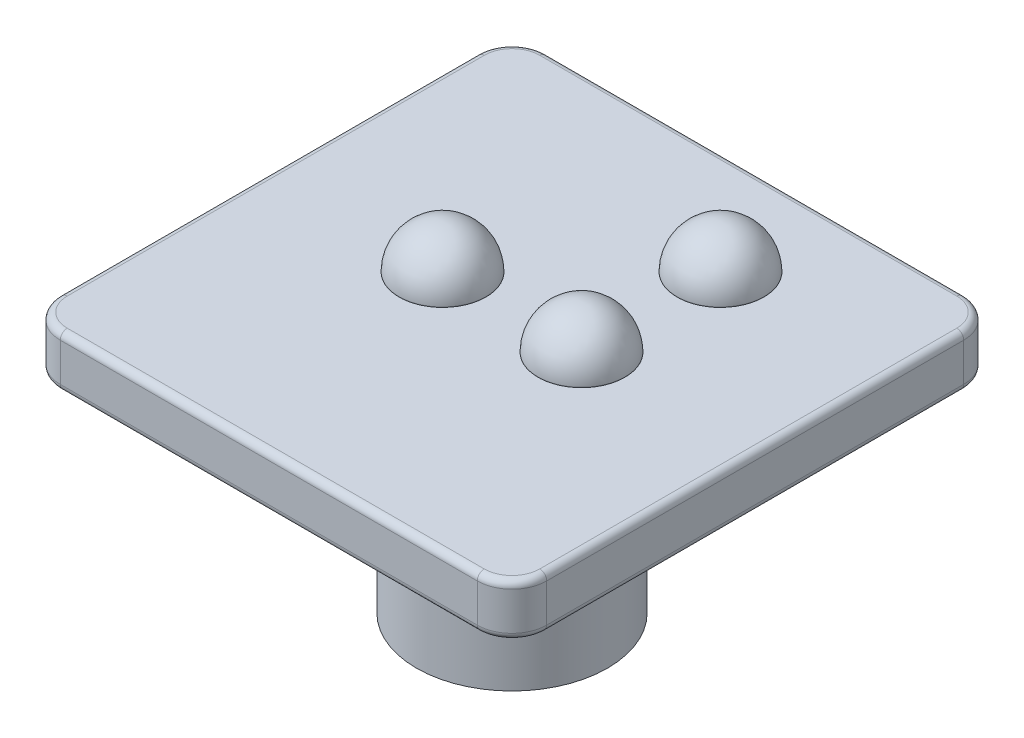
SolidWorks part; units mm, degrees
ref_plane "Front Plane" through (0, 0, 0) normal (0, 0, 1) x (1, 0, 0)
ref_plane "Top Plane" through (0, 0, 0) normal (0, 1, 0) x (1, 0, 0)
ref_plane "Right Plane" through (0, 0, 0) normal (1, 0, 0) x (0, 0, -1)
sketch "Sketch1" plane through (0, 0, 0) normal (0, 1, 0) x (1, 0, 0)
  line L1 (-7.3247, 4.3967) -> (4.6753, 4.3967)
  line L2 (-8.3247, 3.3967) -> (-8.3247, -8.6033)
  line L3 (-7.3247, -9.6033) -> (4.6753, -9.6033)
  line L4 (5.6753, 3.3967) -> (5.6753, -8.6033)
  arc A0 (-8.3247, -8.6033) -> (-7.3247, -9.6033) centre (-7.3247, -8.6033) ccw
  arc A1 (4.6753, -9.6033) -> (5.6753, -8.6033) centre (4.6753, -8.6033) ccw
  arc A2 (4.6753, 4.3967) -> (5.6753, 3.3967) centre (4.6753, 3.3967) cw
  arc A3 (-7.3247, 4.3967) -> (-8.3247, 3.3967) centre (-7.3247, 3.3967) ccw
  point P8 (5.6753, -9.6033)
  point P11 (5.6753, 4.3967)
  point P14 (-8.3247, 4.3967)
  dimension "D3" = 1
  dimension "D1" = 14
  dimension "D2" = 14
extrude "Boss-Extrude1" add sketch "Sketch1" along normal blind 1.5
sketch "Sketch2" plane through (0, 0, 0) normal (0, -1, 0) x (1, 0, 0)
  line L0 (-7.3247, 9.6033) -> (4.6753, 9.6033) construction
  line L1 (5.6753, 8.6033) -> (5.6753, -3.3967) construction
  line L2 (-1.3247, -4.3967) -> (-1.3247, 9.6033) construction
  line L3 (-8.3247, 2.6033) -> (5.6753, 2.6033) construction
  line L4 (-8.3247, -3.3967) -> (-8.3247, 8.6033) construction
  circle A0 centre (-1.3247, 2.6033) radius 2.75
  dimension "D1" = 7
  dimension "D2" = 7
extrude "Boss-Extrude2" add sketch "Sketch2" along normal blind 6
sketch "Sketch3" plane through (0, -6, 0) normal (0, -1, 0) x (1, 0, 0)
  line L0 (-1.3247, 5.3533) -> (-1.3247, -0.1467) construction
  line L1 (-3.3247, 3.1533) -> (0.6753, 3.1533)
  line L2 (-3.3247, 3.1533) -> (-3.3247, 2.0533)
  line L3 (-3.3247, 2.0533) -> (0.6753, 2.0533)
  line L4 (0.6753, 3.1533) -> (0.6753, 2.0533)
  line L5 (-1.8747, 4.6033) -> (-0.7747, 4.6033)
  line L6 (-1.8747, 4.6033) -> (-1.8747, 0.6033)
  line L7 (-1.8747, 0.6033) -> (-0.7747, 0.6033)
  line L8 (-0.7747, 4.6033) -> (-0.7747, 0.6033)
  line L9 (-4.0747, 2.6033) -> (1.4253, 2.6033) construction
  circle A3 centre (-1.3247, 2.6033) radius 2.75 construction
  circle A4 centre (-1.3247, 2.6033) radius 2.75 construction
  dimension "D7" = 0.55
  dimension "D1" = 4
  dimension "D2" = 1.1
  dimension "D3" = 1.1
  dimension "D4" = 4
  dimension "D8" = 0.55
extrude "Cut-Extrude1" cut sketch "Sketch3" against normal blind 6 contours L8 L5 L6 L1 | L1 L8 L3 L4 | L8 L1 L6 L3 | L6 L1 L2 L3 | L8 L3 L6 L7 region at (-2.5997, -6, 2.6033) region at (-1.3247, -6, 3.8783) region at (-1.3247, -6, 2.6033) region at (-0.0497, -6, 2.6033) region at (-1.3247, -6, 1.3283)
chamfer "Chamfer1" distance 0.3 angle 45 12 edges at (-1.3247, -6, 0.6033) (-1.8747, -6, 1.3283) (-2.5997, -6, 2.0533) (-3.3247, -6, 2.6033) (-2.5997, -6, 3.1533) (-0.7747, -6, 1.3283) (-0.0497, -6, 2.0533) (0.6753, -6, 2.6033) (-0.0497, -6, 3.1533) (-0.7747, -6, 3.8783) (-1.3247, -6, 4.6033) (-1.8747, -6, 3.8783)
fillet "Fillet1" radius 1 1 edges at (-1.3247, 0, -0.1467)
sketch "Sketch4" plane through (0, 1.5, 0) normal (0, 1, 0) x (1, 0, 0)
  line L0 (-1.3247, 4.3967) -> (-1.3247, -9.6033) construction
  line L1 (4.6753, 4.3967) -> (-7.3247, 4.3967) construction
  line L2 (-7.3247, -9.6033) -> (4.6753, -9.6033) construction
  line L3 (5.6753, -2.6033) -> (-8.3247, -2.6033) construction
  line L4 (-8.3247, 3.3967) -> (-8.3247, -8.6033) construction
  line L5 (5.6753, -8.6033) -> (5.6753, 3.3967) construction
  line L6 (-3.3247, 4.3967) -> (-3.3247, -9.6033) construction
  line L7 (0.6753, 4.3967) -> (0.6753, -9.6033) construction
  line L8 (-8.3247, 1.3967) -> (5.6753, 1.3967) construction
  line L9 (5.6753, -6.6033) -> (-8.3247, -6.6033) construction
  circle A1 centre (0.6753, -2.6033) radius 1.25
  circle A2 centre (-3.3247, -2.6033) radius 1.25
  circle A5 centre (0.6753, 1.3967) radius 1.25
  dimension "D1" = 4
  dimension "D2" = 4
  dimension "D3" = 2
  dimension "D4" = 2
extrude "Boss-Extrude3" add sketch "Sketch4" along normal blind 0.01
dome "Dome2" faces to dome 1 distance 1.25 reverse direction no elliptical dome no face at (0.6753, 1.51, -0.1467) parameters "D1"=1.25
dome "Dome3" faces to dome 1 distance 1.25 reverse direction no elliptical dome no face at (-3.3247, 1.51, 3.8533) parameters "D1"=1.25
dome "Dome4" faces to dome 1 distance 1.25 reverse direction no elliptical dome no face at (0.6753, 1.51, 3.8533) parameters "D1"=1.25
fillet "Fillet3" radius 0.2 16 edges at (5.3824, 1.5, -4.1038) (5.6753, 1.5, 2.6033) (5.3824, 1.5, 9.3104) (-1.3247, 1.5, 9.6033) (-8.0318, 1.5, 9.3104) (-8.0318, 1.5, -4.1038) (-8.3247, 1.5, 2.6033) (-1.3247, 1.5, -4.3967) (5.3824, 0, 9.3104) (5.6753, 0, 2.6033) (5.3824, 0, -4.1038) (-1.3247, 0, -4.3967) (-8.0318, 0, -4.1038) (-8.3247, 0, 2.6033) (-8.0318, 0, 9.3104) (-1.3247, 0, 9.6033)
